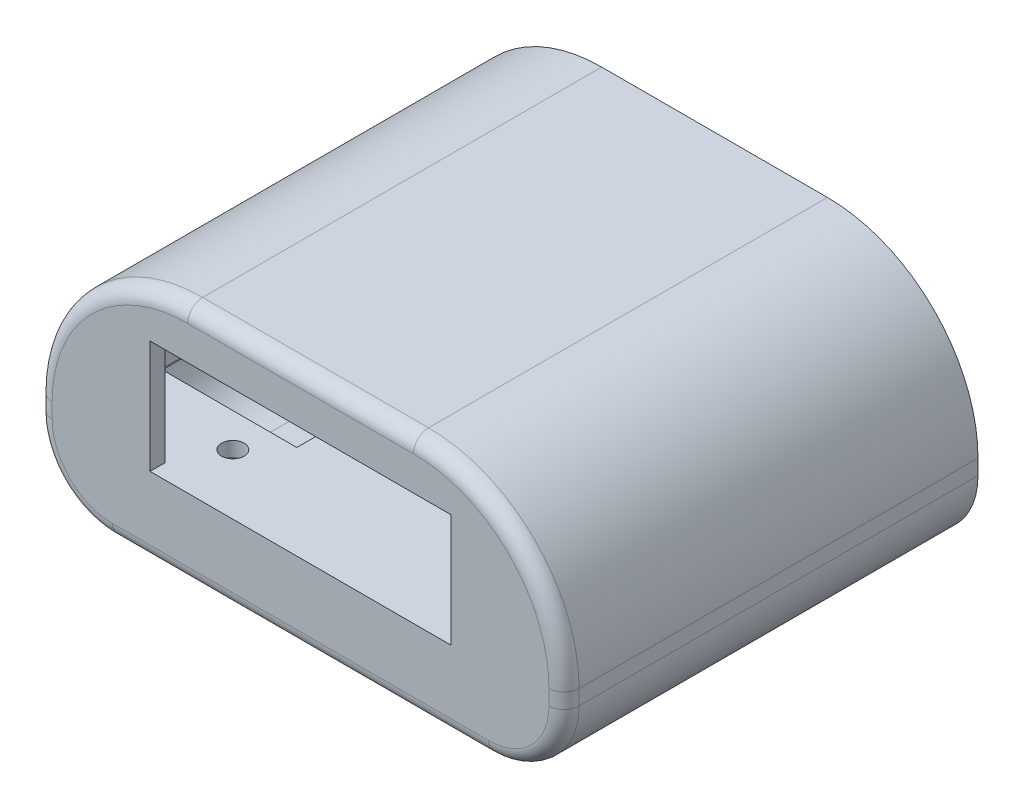
SolidWorks part; units mm, degrees
ref_plane "Front Plane" through (0, 0, 0) normal (0, 0, 1) x (1, 0, 0)
ref_plane "Top Plane" through (0, 0, 0) normal (0, 1, 0) x (1, 0, 0)
ref_plane "Right Plane" through (0, 0, 0) normal (1, 0, 0) x (0, 0, -1)
sketch "Sketch1" plane through (0, 0, 0) normal (0, 0, 1) x (1, 0, 0)
  line L1 (-15, 16) -> (15, 16)
  line L2 (-35, -4) -> (-35, -6)
  line L3 (-25, -16) -> (25, -16)
  line L4 (35, -4) -> (35, -6)
  line L5 (-35, 16) -> (35, -16) construction
  line L6 (-35, -16) -> (35, 16) construction
  arc A0 (25, -16) -> (35, -6) centre (25, -6) ccw
  arc A1 (-35, -6) -> (-25, -16) centre (-25, -6) ccw
  arc A2 (15, 16) -> (35, -4) centre (15, -4) cw
  arc A3 (-15, 16) -> (-35, -4) centre (-15, -4) ccw
  point P0 (0, 0)
  dimension "D1" = 20
  dimension "D4" = 10
  dimension "D2" = 70
  dimension "D3" = 32
extrude "Boss-Extrude1" add sketch "Sketch1" along normal blind 55
shell "Shell1" thickness 2 removed face at (0, -1.9822, 0)
sketch "Sketch2" plane through (0, 0, 0) normal (0, 0, -1) x (-1, 0, 0)
  line L0 (-15, 16) -> (15, 16) construction
  line L1 (-15, 4.48) -> (-30.8773, 4.48)
  line L2 (-15, 4.48) -> (-15, 14)
  line L3 (0, 14) -> (0, -14) construction
  line L4 (-15, 14) -> (15, 14) construction
  line L5 (25, -14) -> (-25, -14) construction
  line L6 (15, 4.48) -> (15, 14)
  line L7 (15, 4.48) -> (30.8773, 4.48)
  arc A0 (-15, 14) -> (-33, -4) centre (-15, -4) ccw construction
  arc A1 (-30.8773, 4.48) -> (-15, 14) centre (-15, -4) cw
  arc A2 (30.8773, 4.48) -> (15, 14) centre (15, -4) ccw
  dimension "D1" = 11.52
extrude "Boss-Extrude2" add sketch "Sketch2" against normal blind 10 contours L7 A2 L6 | L1 A1 L2
hole_wizard "M3x0.5 Tapped Hole1" positions "Sketch3" profile "Sketch4" tap size "M3x0.5" standard "ANSI Metric"
sketch "Sketch3" plane through (0, 0, 0) normal (0, 0, -1) x (-1, 0, 0)
  line L0 (-15, 16) -> (15, 16) construction
  line L1 (-35, -6) -> (-35, -4) construction
  line L2 (35, -4) -> (35, -6) construction
  point P0 (-18.4, 8)
  point P10 (21.6, 8)
  dimension "D1" = 8
  dimension "D2" = 16.6
  dimension "D3" = 13.4
sketch "Sketch4" plane through (18.4, 8, 0) normal (1, 0, 0) x (0, 1, 0)
  line L0 (0, 0) -> (0, 8.2511)
  line L1 (0, 8.2511) -> (1.25, 7.5)
  line L2 (1.25, 7.5) -> (1.25, 0)
  line L5 (1.25, 0) -> (0, 0)
  line L10 (0, 8.2511) -> (-1.25, 7.5) construction
  line L11 (0, -6.35) -> (0, 107.95) construction
  dimension "Tap Drill Dia." = 2.5
  dimension "Tap Drill Depth" = 7.5
  dimension "Drill Angle" = 118
sketch "Sketch5" plane through (0, 0, 0) normal (0, 0, -1) x (-1, 0, 0)
  line L1 (-33, -5.52) -> (33, -5.52)
  line L2 (-33, -5.52) -> (-33, -7.52)
  line L3 (-33, -7.52) -> (33, -7.52)
  line L4 (33, -5.52) -> (33, -7.52)
  line L5 (33, -4) -> (33, -6) construction
  line L7 (-15, 16) -> (15, 16) construction
  dimension "D1" = 21.52
  dimension "D2" = 2
extrude "Boss-Extrude3" add sketch "Sketch5" against normal up to next contours L1 L4 L3 L2
sketch "Sketch6" plane through (0, 0, 53) normal (0, 0, -1) x (-1, 0, 0)
  line L0 (-33, -5.52) -> (33, -5.52) construction
  line L1 (-20, -5.52) -> (20, -5.52)
  line L2 (-20, -5.52) -> (-20, 9.48)
  line L3 (-20, 9.48) -> (20, 9.48)
  line L4 (20, -5.52) -> (20, 9.48)
  point P6 (0, 9.48)
  dimension "D1" = 15
  dimension "D2" = 40
extrude "Cut-Extrude1" cut sketch "Sketch6" against normal blind 10
hole_wizard "Ø3.0mm Dowel Hole1" positions "Sketch7" profile "Sketch8" hole size "Ø3.0" standard "AS"
sketch "Sketch7" plane through (0, -5.52, 0) normal (0, 1, 0) x (1, 0, 0)
  line L0 (17, -34.5) -> (-17, -47) construction
  line L2 (-20, -55) -> (20, -55) construction
  line L3 (-17, -47) -> (-17, -22) construction
  point P0 (-17, -47)
  point P2 (-17, -22)
  point P4 (17, -34.5)
  point P11 (0, -40.75)
  point P14 (0, -55)
  point P20 (-17, -34.5)
  dimension "D1" = 25
  dimension "D2" = 34
  dimension "D3" = 8
sketch "Sketch8" plane through (-17, -5.52, 47) normal (1, 0, 0) x (0, 0, 1)
  line L0 (0, 0) -> (0, 4.9013)
  line L1 (0, 4.9013) -> (1.5, 4)
  line L2 (1.5, 4) -> (1.5, 0)
  line L5 (1.5, 0) -> (0, 0)
  line L10 (0, 4.9013) -> (-1.5, 4) construction
  line L11 (0, -6.35) -> (0, 107.95) construction
  dimension "Hole Dia." = 3
  dimension "Hole Depth" = 4
  dimension "Drill Angle" = 118
sketch "Sketch9" plane through (0, -5.52, 0) normal (0, 1, 0) x (1, 0, 0)
  line L0 (-33, -53) -> (-33, 0) construction
  line L1 (-33, -26.5) -> (-13, -26.5)
  line L2 (-33, -26.5) -> (-33, -42.5)
  line L3 (-33, -42.5) -> (-13, -42.5)
  line L4 (-13, -26.5) -> (-13, -42.5)
  line L5 (-17, -47) -> (-17, -22) construction
  point P6 (-17, -34.5)
  point P7 (-13, -34.5)
  dimension "D1" = 20
extrude "Cut-Extrude2" cut sketch "Sketch9" against normal up to surface (2 mm away) up to face at (-17, -7.52, 45.5)
fillet "Fillet1" radius 2 8 edges at (35, -5, 55) (32.0711, -13.0711, 55) (0, -16, 55) (-32.0711, -13.0711, 55) (-35, -5, 55) (-29.1421, 10.1421, 55) (0, 16, 55) (29.1421, 10.1421, 55)
